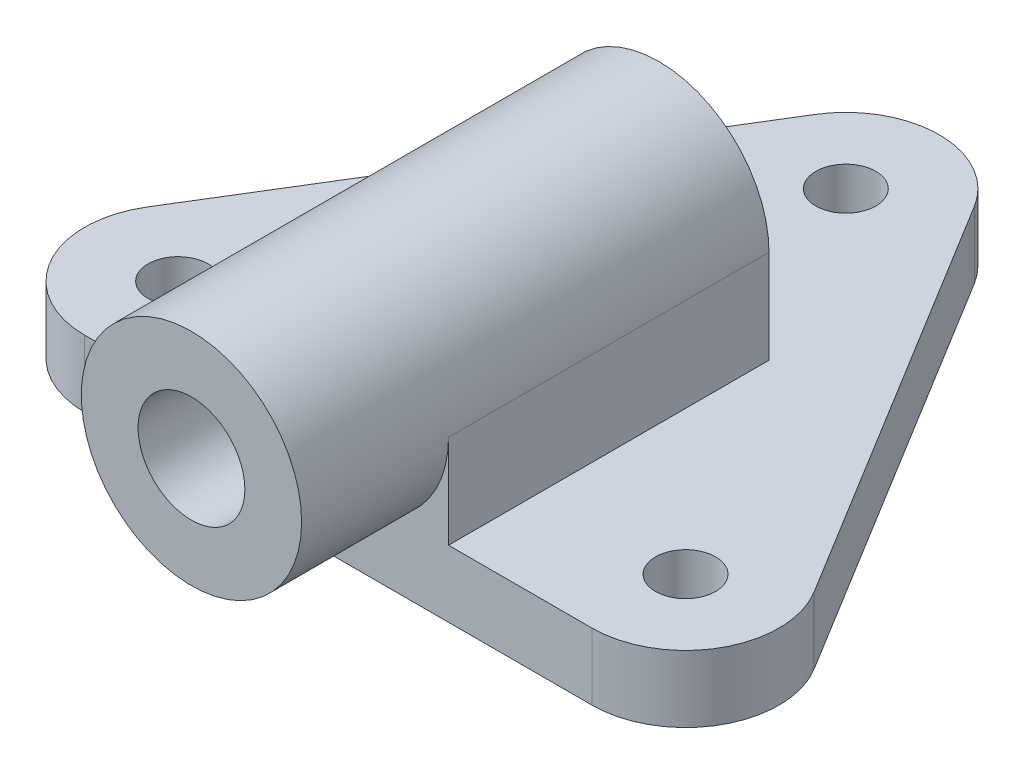
SolidWorks part; units mm, degrees
ref_plane "Front Plane" through (0, 0, 0) normal (0, 0, 1) x (1, 0, 0)
ref_plane "Top Plane" through (0, 0, 0) normal (0, 1, 0) x (1, 0, 0)
ref_plane "Right Plane" through (0, 0, 0) normal (1, 0, 0) x (0, 0, -1)
sketch "Sketch2" plane through (0, 0, 0) normal (0, 1, 0) x (1, 0, 0)
  line L0 (0, 0) -> (31470.8818, 0) construction
  line L1 (0, 0) -> (0, 31470.8818) construction
  line L2 (11.9364, 69.3159) -> (49.9364, 7.3159)
  line L3 (-38, -14) -> (38, -14)
  line L4 (-11.9364, 69.3159) -> (-49.9364, 7.3159)
  circle A0 centre (0, 62) radius 4.5
  arc A1 (11.9364, 69.3159) -> (-11.9364, 69.3159) centre (0, 62) ccw
  circle A2 centre (38, 0) radius 4.5
  arc A3 (38, -14) -> (49.9364, 7.3159) centre (38, 0) ccw
  circle A4 centre (-38, 0) radius 4.5
  arc A5 (-38, -14) -> (-49.9364, 7.3159) centre (-38, 0) cw
  dimension "D1" = 28
  dimension "D2" = 9
  dimension "D5" = 9
  dimension "D6" = 28
  dimension "D3" = 62
  dimension "D4" = 76
extrude "Boss-Extrude1" add sketch "Sketch2" along normal blind 10
sketch "Sketch3" plane through (0, 0, 14) normal (0, 0, 1) x (1, 0, 0)
  line L0 (0, 0) -> (0, 50000) construction
  line L1 (-38, 0) -> (38, 0) construction
  line L2 (38, 0) -> (52, 0) construction
  line L3 (-38, 10) -> (38, 10) construction
  line L4 (-38, 10) -> (-16.5, 10)
  line L5 (-16.5, 24) -> (-16.5, 10)
  line L6 (16.5, 24) -> (16.5, 10)
  line L7 (-8.7321, 10) -> (38, 10)
  circle A1 centre (0, 24) radius 16.5
  point P4 (0, 0)
  line M5 (38, 10) -> (-38, 10)
  dimension "D2" = 33
  dimension "D1" = 24
extrude "Boss-Extrude5" add sketch "Sketch3" along normal blind 22 and the other way blind 48 contours L0 A1 M5 | L0 L7 A1 | L0 A1 L7 | A1 L0 M5 region at (-3.3104, 8.9932, 14) region at (3.3104, 8.9932, 14) region at (-7.1351, 24.5376, 14) region at (7.1351, 24.5376, 14)
extrude "Boss-Extrude6" add sketch "Sketch3<7>" against normal blind 48 contours A1 L6 M5 | A1 L5 M5 region at (-14.3074, 13.3143, 14) region at (14.3074, 13.3143, 14)
sketch "Sketch3<7>" plane through (0, 0, 14) normal (0, 0, 1) x (1, 0, 0) same geometry as "Sketch3"
hole_wizard "Ø16.0mm Dowel Hole1" positions "Sketch4" profile "Sketch5" hole size "Ø16.0" standard "ISO"
sketch "Sketch4" plane through (0, 0, 36) normal (0, 0, 1) x (1, 0, 0)
  point P0 (0, 24)
sketch "Sketch5" plane through (0, 24, 36) normal (1, 0, 0) x (0, -1, 0)
  line L0 (0, 0) -> (0, 58.8069)
  line L1 (0, 58.8069) -> (8, 54)
  line L2 (8, 54) -> (8, 0)
  line L5 (8, 0) -> (0, 0)
  line L10 (0, 58.8069) -> (-8, 54) construction
  line L11 (0, -6.35) -> (0, 107.95) construction
  dimension "Hole Dia." = 16
  dimension "Hole Depth" = 54
  dimension "Drill Angle" = 118
